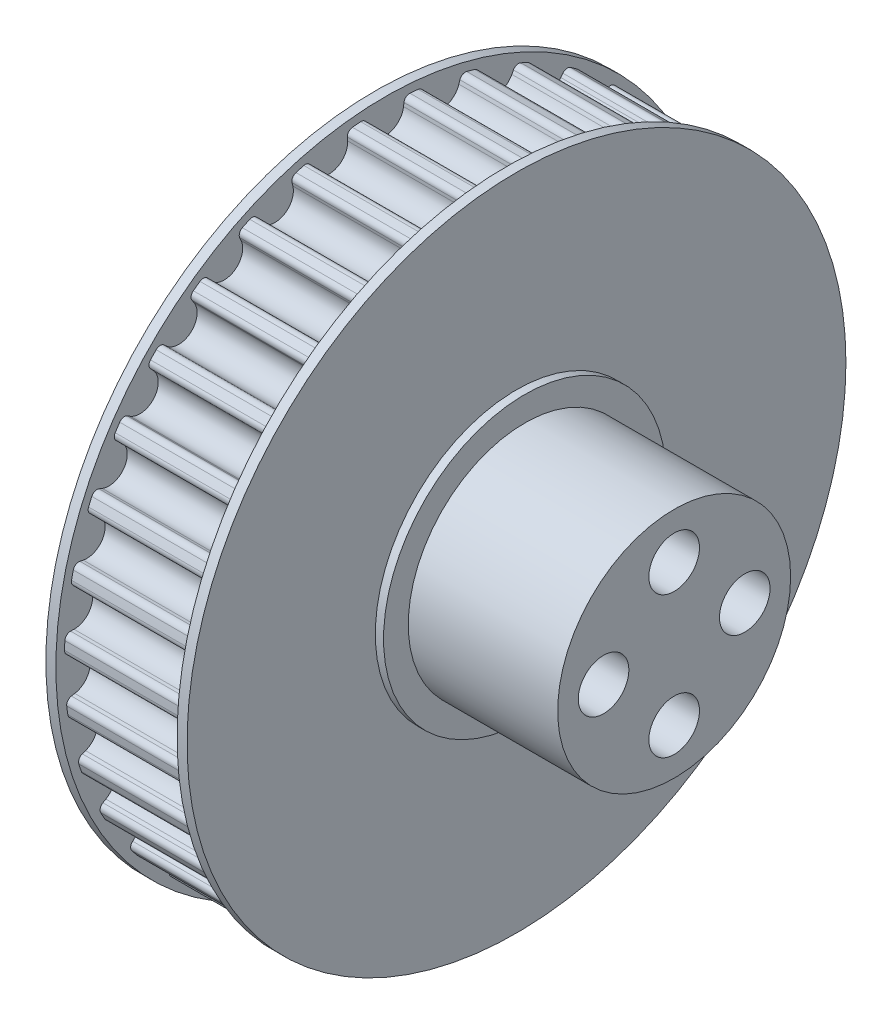
SolidWorks part; units mm, degrees
material "ABS"
ref_plane "前视基准面" through (0, 0, 0) normal (0, 0, 1) x (1, 0, 0)
ref_plane "上视基准面" through (0, 0, 0) normal (0, 1, 0) x (1, 0, 0)
ref_plane "右视基准面" through (0, 0, 0) normal (1, 0, 0) x (0, 0, -1)
sketch "草图1" plane through (0, 0, 0) normal (0, 0, 1) x (1, 0, 0)
  line L0 (0, 0) -> (64.8368, 0) construction
  line L1 (0, 0) -> (0, 27.278)
  line L2 (0, 27.278) -> (10.3, 27.278)
  line L3 (10.3, 27.278) -> (10.3, 0)
  line L6 (10.3, 0) -> (0, 0)
  dimension "B" = 10.3
  dimension "da" = 54.556
revolve "旋转1" add sketch "草图1" angle 360 about L0
ref_axis "基准轴1" through (-1, 0, 0) along (1, 0, 0)
sketch "草图6" plane through (0, 0, 0) normal (1, 0, 0) x (0, 0, -1)
  line L0 (0, 0) -> (0, 30.6512) construction
  line L1 (1.5839, 26.7772) -> (1.5484, 26.4879)
  line L2 (2.5954, 27.1543) -> (2.792, 28.7558)
  line L3 (-2.5954, 27.1543) -> (-2.792, 28.7558)
  line L4 (-1.5839, 26.7772) -> (-1.5484, 26.4879)
  circle A0 centre (0, 0) radius 27.278 construction
  circle A1 centre (0, 0) radius 25.118 construction
  arc A2 (-1.5484, 26.4879) -> (1.5484, 26.4879) centre (0, 26.678) ccw
  arc A3 (2.792, 28.7558) -> (-2.792, 28.7558) centre (0, 0) ccw
  arc A4 (1.5839, 26.7772) -> (2.0972, 27.1973) centre (2.0603, 26.7187) cw
  arc A5 (2.0972, 27.1973) -> (2.5954, 27.1543) centre (0, 0) cw
  arc A6 (-2.0972, 27.1973) -> (-2.5954, 27.1543) centre (0, 0) ccw
  arc A7 (-1.5839, 26.7772) -> (-2.0972, 27.1973) centre (-2.0603, 26.7187) ccw
  circle A8 centre (0, 0) radius 27.278 construction
  point P7 (0, 3.25)
  point P8 (0, 28.4912)
  point P15 (1.6393, 27.2287)
  dimension "ra" = 0.48
  dimension "rf" = 1.56
  dimension "hg" = 2.16
  dimension "D3" = 0.5
  dimension "D4" = 1.6136
  dimension "angle" = 14
  dimension "bw" = 3.25
  dimension "D1" = 2.16
extrude "切除-拉伸2" cut sketch "草图6" along normal up to next
pattern_circular "阵列(圆周)3" count 35 over 360 about axis through (-1, 0, 0) along (1, 0, 0) of "切除-拉伸2"
sketch "草图7" plane through (10.3, 0, 0) normal (1, 0, 0) x (0, 0, -1)
  circle A0 centre (0, 0) radius 28
  dimension "D1" = 56
extrude "凸台-拉伸1" add sketch "草图7" along normal blind 0.85
sketch "草图8" plane through (11.15, 0, 0) normal (1, 0, 0) x (0, 0, -1)
  circle A0 centre (0, 0) radius 12
  dimension "D1" = 24
extrude "凸台-拉伸2" add sketch "草图8" along normal blind 0.7
sketch "草图9" plane through (11.85, 0, 0) normal (1, 0, 0) x (0, 0, -1)
  circle A0 centre (0, 0) radius 9.9
  dimension "D1" = 19.8
extrude "凸台-拉伸3" add sketch "草图9" along normal blind 4
ref_plane "基准面1" through (5.15, 0, 0) normal (-1, 0, 0) x (0, 0, 1)
mirror "镜向1" about plane through (5.15, 0, 0) normal (-1, 0, 0) of "凸台-拉伸3", "凸台-拉伸2", "凸台-拉伸1"
sketch "草图10" plane through (15.85, 0, 0) normal (1, 0, 0) x (0, 0, -1)
  circle A0 centre (0, 0) radius 6 construction
  circle A1 centre (0, 6) radius 2.15
  circle A2 centre (6, 0) radius 2.15
  circle A3 centre (0, -6) radius 2.15
  circle A4 centre (-6, 0) radius 2.15
  dimension "D1" = 12
  dimension "D2" = 4.3
  dimension "D3" = 4
extrude "切除-拉伸3" cut sketch "草图10" against normal through all
sketch "草图11" plane through (15.85, 0, 0) normal (1, 0, 0) x (0, 0, -1)
  circle A0 centre (-6, 0) radius 2.15 construction
  circle A1 centre (0, 0) radius 9.9
  circle A2 centre (0, 0) radius 9.9
  circle A3 centre (0, -6) radius 2.15 construction
  circle A4 centre (6, 0) radius 2.15 construction
  circle A5 centre (0, 6) radius 2.15 construction
  circle A6 centre (-6, 0) radius 2.15
  circle A7 centre (0, -6) radius 2.15
  circle A8 centre (6, 0) radius 2.15
  circle A9 centre (0, 6) radius 2.15
  dimension "D1" = 0
extrude "凸台-拉伸4" add sketch "草图11" along normal blind 8.7
sketch "草图12" plane through (-5.55, 0, 0) normal (-1, 0, 0) x (0, 0, 1)
  circle A0 centre (6, 0) radius 2.15 construction
  circle A1 centre (0, 0) radius 9.9
  circle A2 centre (0, 0) radius 9.9
  circle A3 centre (0, -6) radius 2.15 construction
  circle A4 centre (0, 6) radius 2.15 construction
  circle A5 centre (-6, 0) radius 2.15 construction
  circle A6 centre (6, 0) radius 2.15
  circle A7 centre (0, -6) radius 2.15
  circle A8 centre (0, 6) radius 2.15
  circle A9 centre (-6, 0) radius 2.15
  dimension "D1" = 0
extrude "凸台-拉伸5" add sketch "草图12" along normal blind 6.65
equation "\"D3@草图6\" = \"ra@草图6\""
